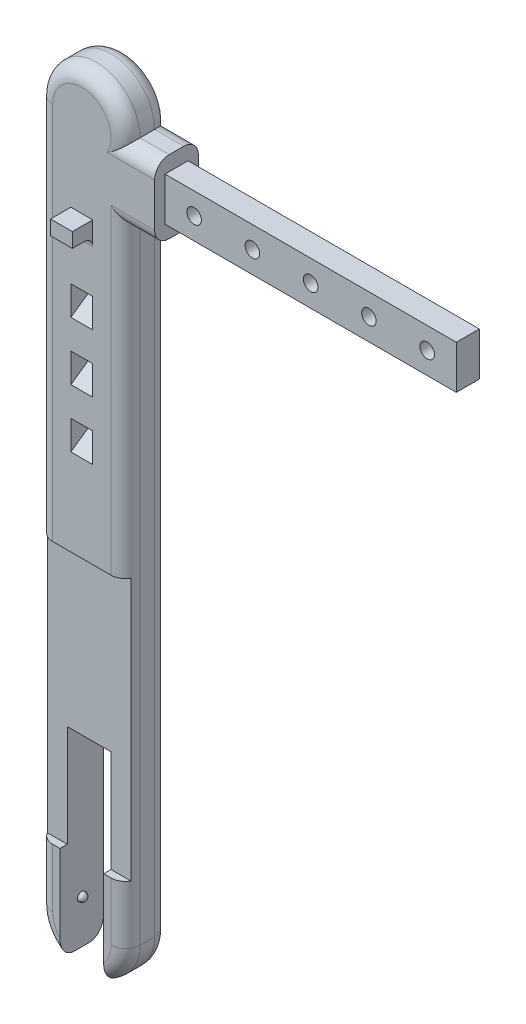
SolidWorks part; units mm, degrees
ref_plane "Front Plane" through (0, 0, 0) normal (0, 0, 1) x (1, 0, 0)
ref_plane "Top Plane" through (0, 0, 0) normal (0, 1, 0) x (1, 0, 0)
ref_plane "Right Plane" through (0, 0, 0) normal (1, 0, 0) x (0, 0, -1)
sketch "Sketch1" plane through (0, 0, 0) normal (0, 0, 1) x (1, 0, 0)
  line L0 (0, 124.9367) -> (0, -115.0633) construction
  line L1 (15, 99.9367) -> (15, -115.0633)
  line L2 (-15, 124.9367) -> (-15, -115.0633)
  line L3 (15, 124.9367) -> (25, 124.9367)
  line L4 (25, 124.9367) -> (25, 99.9367)
  line L5 (25, 99.9367) -> (15, 99.9367)
  arc A0 (15, 124.9367) -> (-15, 124.9367) centre (0, 124.9367) ccw
  arc A1 (-15, -115.0633) -> (15, -115.0633) centre (0, -115.0633) ccw
  point P3 (0, 4.9367)
  dimension "D2" = 15
  dimension "D1" = 240
  dimension "D3" = 10
  dimension "D4" = 25
extrude "Boss-Extrude1" add sketch "Sketch1" along normal mid plane 15
fillet "Fillet1" radius 5 12 edges at (0, 139.9367, -7.5) (-15, 4.9367, -7.5) (0, -130.0633, -7.5) (0, 139.9367, 7.5) (-15, 4.9367, 7.5) (0, -130.0633, 7.5) (20, 99.9367, -7.5) (20, 124.9367, -7.5) (20, 124.9367, 7.5) (20, 99.9367, 7.5) (15, -7.5633, -7.5) (15, -7.5633, 7.5)
sketch "Sketch2" plane through (25, 0, 0) normal (1, 0, 0) x (0, 0, -1)
  line L0 (7.5, 104.9367) -> (7.5, 119.9367) construction
  line L1 (-3.95, 119.8867) -> (3.95, 119.8867)
  line L2 (-3.95, 119.8867) -> (-3.95, 104.9867)
  line L3 (-3.95, 104.9867) -> (3.95, 104.9867)
  line L4 (3.95, 119.8867) -> (3.95, 104.9867)
  line L5 (-2.5, 124.9367) -> (2.5, 124.9367) construction
  dimension "D1" = 7.9
  dimension "D2" = 14.9
  dimension "D3" = 3.55
  dimension "D4" = 5.05
extrude "Boss-Extrude2" add sketch "Sketch2" along normal blind 100
sketch "Sketch3" plane through (0, 0, 3.95) normal (0, 0, 1) x (1, 0, 0)
  line L0 (25, 104.9367) -> (25, 119.9367) construction
  line L1 (125, 119.8867) -> (25, 119.8867) construction
  circle A0 centre (35, 112.4367) radius 2.5
  circle A1 centre (55, 112.4367) radius 2.5
  circle A2 centre (75, 112.4367) radius 2.5
  circle A3 centre (95, 112.4367) radius 2.5
  circle A4 centre (115, 112.4367) radius 2.5
  dimension "D2" = 5
  dimension "D1" = 10
  dimension "D3" = 7.45
  dimension "D4" = 5
extrude "Cut-Extrude1" cut sketch "Sketch3" against normal blind 100
sketch "Sketch4" plane through (0, 0, 7.5) normal (0, 0, 1) x (1, 0, 0)
  line L0 (-10, 124.9367) -> (-10, -115.0633) construction
  line L1 (-7.5, -130.0633) -> (7.5, -130.0633)
  line L2 (-7.5, -130.0633) -> (-7.5, -60.0633)
  line L3 (-7.5, -60.0633) -> (7.5, -60.0633)
  line L4 (7.5, -130.0633) -> (7.5, -60.0633)
  arc A0 (-15, -115.0633) -> (15, -115.0633) centre (0, -115.0633) ccw construction
  dimension "D1" = 70
  dimension "D2" = 15
  dimension "D3" = 2.5
extrude "Cut-Extrude2" cut sketch "Sketch4" against normal blind 100
sketch "Sketch7" plane through (0, 0, 0) normal (1, 0, 0) x (0, 0, -1)
  line L1 (-7.5, 124.9367) -> (-7.5, -115.0633) construction
  line L5 (0, -41.6141) -> (0, 18.3597) construction
  line L6 (0, 69.9367) -> (-7.5, 64.6852)
  line L7 (0, 79.9367) -> (-7.5, 74.6852)
  line L8 (-7.5, 74.6852) -> (-7.5, 64.6852)
  line L10 (0, 69.9367) -> (0, 79.9367)
  line L11 (0, 49.9367) -> (0, 59.9367)
  line L12 (0, 59.9367) -> (-7.5, 54.6852)
  line L13 (-7.5, 54.6852) -> (-7.5, 44.6852)
  line L14 (-7.5, 44.6852) -> (0, 49.9367)
  line L15 (0, 29.9367) -> (0, 39.9367)
  line L16 (0, 39.9367) -> (-7.5, 34.6852)
  line L17 (-7.5, 34.6852) -> (-7.5, 24.6852)
  line L18 (-7.5, 24.6852) -> (0, 29.9367)
  line L23 (-2.5, 124.9367) -> (2.5, 124.9367) construction
  line L24 (0, 9.9367) -> (0, 19.9367) [skipped]
  line L25 (0, 19.9367) -> (-7.5, 14.6852) [skipped]
  line L26 (-7.5, 14.6852) -> (-7.5, 4.6852) [skipped]
  dimension "D1" = 45
  dimension "D2" = 10
  dimension "D6" = 55
  dimension "D8" = 4
extrude "Cut-Extrude3" cut sketch "Sketch7" against normal mid plane 7.5
sketch "Sketch8" plane through (0, 0, 0) normal (0, 0, 1) x (1, 0, 0)
  line L0 (-28.1388, -113.0633) -> (31.3541, -113.0633) construction
  line L1 (7.5, -60.0633) -> (-7.5, -60.0633) construction
  line L2 (-7.5, -113.0633) -> (-6, -113.0633)
  line L3 (-7.5, -60.0633) -> (-7.5, -121.6777) construction
  line L4 (-7.5, -111.5633) -> (-7.5, -113.0633)
  line L5 (7.5, -113.0633) -> (6, -113.0633)
  line L6 (7.5, -121.6777) -> (7.5, -60.0633) construction
  line L7 (7.5, -111.5633) -> (7.5, -113.0633)
  arc A0 (-6, -113.0633) -> (-7.5, -111.5633) centre (-7.5, -113.0633) ccw
  arc A1 (6, -113.0633) -> (7.5, -111.5633) centre (7.5, -113.0633) cw
  dimension "D1" = 53
  dimension "D2" = 1.5
  dimension "D3" = 1.5
revolve "Revolve1" add sketch "Sketch8" angle 360 about L0
sketch "Sketch9" plane through (0, 0, 0) normal (1, 0, 0) x (0, 0, -1)
  line L0 (-7.5, 89.4367) -> (-7.5, 97.4367)
  line L1 (-7.5, 124.9367) -> (-7.5, -115.0633) construction
  line L2 (-7.5, 97.4367) -> (-14.5, 97.4367)
  line L3 (-14.5, 97.4367) -> (-14.5, 92.4367)
  line L5 (-14.5, 92.4367) -> (-10.5, 92.4367)
  arc A2 (-10.5, 92.4367) -> (-7.5, 89.4367) centre (-10.5, 89.4367) cw
  dimension "D4" = 3
  dimension "D1" = 15.5
  dimension "D2" = 7
  dimension "D3" = 5
extrude "Boss-Extrude3" add sketch "Sketch9" along normal mid plane 7.5
sketch "Sketch10" plane through (-15, 0, 0) normal (-1, 0, 0) x (0, 0, 1)
  line L0 (7.5, -95.0633) -> (5, -95.0633)
  line L1 (7.5, 124.9367) -> (7.5, -115.0633) construction
  line L2 (5, -95.0633) -> (5, -5.0633)
  line L3 (5, -5.0633) -> (7.5, -5.0633)
  line L4 (7.5, -5.0633) -> (7.5, -95.0633)
  line L5 (2.5, -115.0633) -> (7.5, -115.0633) construction
  dimension "D1" = 2.5
  dimension "D2" = 90
  dimension "D3" = 20
extrude "Cut-Extrude4" cut sketch "Sketch10" against normal through all
